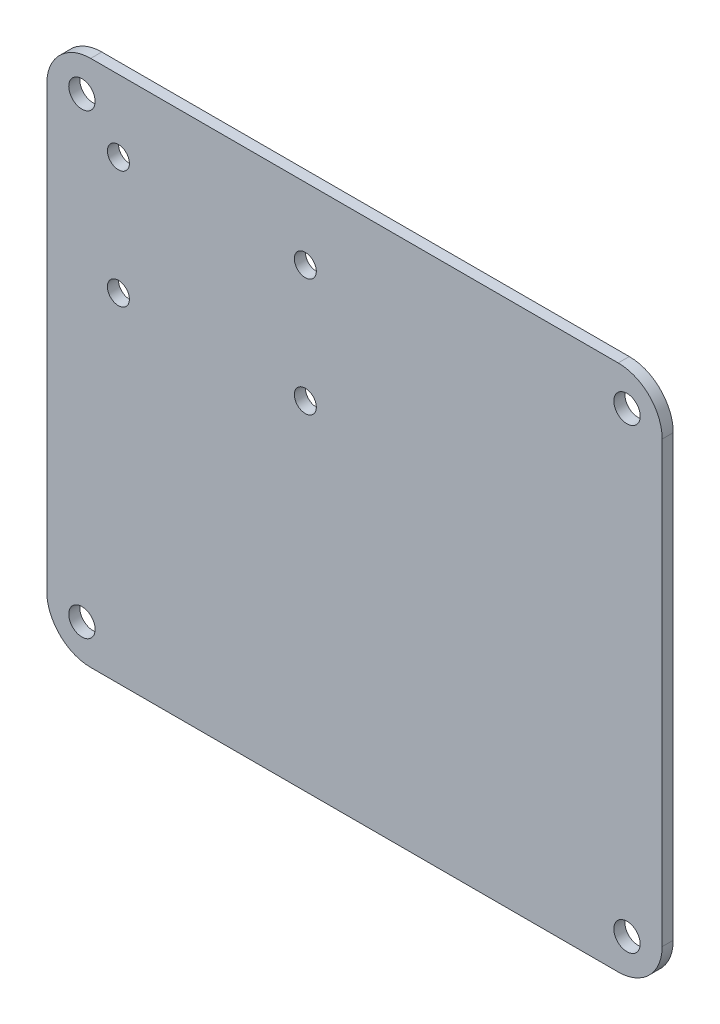
SolidWorks part; units mm, degrees
ref_plane "Front Plane" through (0, 0, 0) normal (0, 0, 1) x (1, 0, 0)
ref_plane "Top Plane" through (0, 0, 0) normal (0, 1, 0) x (1, 0, 0)
ref_plane "Right Plane" through (0, 0, 0) normal (1, 0, 0) x (0, 0, -1)
sketch "Sketch1" plane through (0, 0, 0) normal (0, 0, 1) x (1, 0, 0)
  line L1 (-15.4905, -8.0369) -> (73.4095, -8.0369)
  line L2 (-15.4905, -8.0369) -> (-15.4905, 68.1631)
  line L3 (-15.4905, 68.1631) -> (73.4095, 68.1631)
  line L4 (73.4095, -8.0369) -> (73.4095, 68.1631)
  line L8 (25.8595, 61.8131) -> (-9.1405, 61.8131) construction
  line L9 (-9.1405, 61.8131) -> (-9.1405, 36.8131) construction
  dimension "D1" = 76.2
  dimension "D2" = 88.9
  dimension "D3" = 6.35
  dimension "D4" = 6.35
extrude "Boss-Extrude1" add sketch "Sketch1" along normal blind 1.6
sketch "Sketch2" plane through (0, 0, 0) normal (0, 0, -1) x (-1, 0, 0)
  circle A0 centre (5.1405, 57.8131) radius 1.5875 construction
  circle A1 centre (-21.8595, 57.8131) radius 1.5875 construction
  circle A2 centre (-21.8595, 40.8131) radius 1.5875 construction
  circle A3 centre (5.1405, 40.8131) radius 1.5875 construction
  circle A4 centre (5.1405, 57.8131) radius 1.5875
  circle A5 centre (-21.8595, 57.8131) radius 1.5875
  circle A6 centre (-21.8595, 40.8131) radius 1.5875
  circle A7 centre (5.1405, 40.8131) radius 1.5875
extrude "Cut-Extrude1" cut sketch "Sketch2" against normal through all
sketch "Sketch4" plane through (0, 0, 0) normal (0, 0, -1) x (-1, 0, 0)
  line L0 (-28.9595, 68.1631) -> (-28.9595, -8.0369) construction
  line L1 (-73.4095, 68.1631) -> (15.4905, 68.1631) construction
  line L2 (15.4905, -8.0369) -> (-73.4095, -8.0369) construction
  line L3 (-73.4095, 30.0631) -> (15.4905, 30.0631) construction
  line L4 (-73.4095, -8.0369) -> (-73.4095, 68.1631) construction
  line L5 (15.4905, 68.1631) -> (15.4905, -8.0369) construction
  circle A0 centre (10.4105, 63.0831) radius 1.905
  circle A1 centre (-68.3295, 63.0831) radius 1.905
  circle A2 centre (-68.3295, -2.9569) radius 1.905
  circle A3 centre (10.4105, -2.9569) radius 1.905
  dimension "D1" = 3.81
  dimension "D2" = 5.08
  dimension "D3" = 5.08
extrude "Cut-Extrude2" cut sketch "Sketch4" against normal through all
fillet "Fillet1" radius 6.35 4 edges at (73.4095, 68.1631, 0.8) (73.4095, -8.0369, 0.8) (-15.4905, -8.0369, 0.8) (-15.4905, 68.1631, 0.8)
sketch "Sketch5" plane through (0, 0, 1.6) normal (0, 0, 1) x (1, 0, 0)
  line L0 (-15.4905, 61.8131) -> (-15.4905, -1.6869) construction
  line L1 (-9.1405, -8.0369) -> (67.0595, -8.0369) construction
  line L2 (67.0595, 68.1631) -> (-9.1405, 68.1631) construction
  line L7 (-9.1405, 61.8131) -> (-9.1405, 36.8131)
  line L8 (-9.1405, 36.8131) -> (25.8595, 36.8131)
  line L9 (25.8595, 36.8131) -> (25.8595, 61.8131)
  line L10 (25.8595, 61.8131) -> (-9.1405, 61.8131)
  line L11 (-9.1405, 61.8131) -> (-9.1405, 36.8131)
  line L12 (-9.1405, 36.8131) -> (25.8595, 36.8131)
  line L13 (25.8595, 36.8131) -> (25.8595, 61.8131)
  line L14 (25.8595, 61.8131) -> (-9.1405, 61.8131)
  circle A0 centre (-10.4105, -2.9569) radius 1.905 construction
  circle A1 centre (-5.1405, 40.8131) radius 1.5875 construction
  circle A2 centre (-5.1405, 40.8131) radius 1.5875
  circle A3 centre (-10.4105, -2.9569) radius 1.905
  circle A4 centre (15.8595, 42.8131) radius 3 construction
  circle A5 centre (1.8595, 49.3131) radius 2.3813
  circle A6 centre (1.8595, 49.3131) radius 2.3813
  circle A7 centre (15.8595, 55.8131) radius 3 construction
  circle A8 centre (15.8595, 42.8131) radius 3
  circle A9 centre (15.8595, 55.8131) radius 3
  point P0 (-10.4105, 63.0831)
  point P1 (-10.4105, -2.9569)
  point P3 (68.3295, -2.9569)
  point P5 (68.3295, 63.0831)
  point P7 (-5.1405, 57.8131)
  point P9 (-5.1405, 40.8131)
  point P11 (21.8595, 40.8131)
  point P13 (21.8595, 57.8131)
  point P15 (-15.4905, -8.0369)
  point P30 (-15.4905, 68.1631)
  dimension "D9" = 3.175
  dimension "D10" = 3.81
  dimension "D2" = 5.08
  dimension "D3" = 10.35
  dimension "D4" = 27.35
  dimension "D5" = 71.12
  dimension "D6" = 10.35
  dimension "D7" = 37.35
  dimension "D8" = 83.82
  dimension "D12" = 31.35
  dimension "D13" = 25.35
  dimension "D14" = 12.35
  dimension "D15" = 18.85
  dimension "D16" = 17.35
  dimension "D18" = 6.35
  dimension "D19" = 6.35
  dimension "D20" = 41.35
  dimension "D21" = 31.35
  dimension "D11" = 0
  dimension "D17" = 0
ref_plane "Plane1" through (28.9595, 0, 0) normal (-1, 0, 0) x (0, 0, 1)
